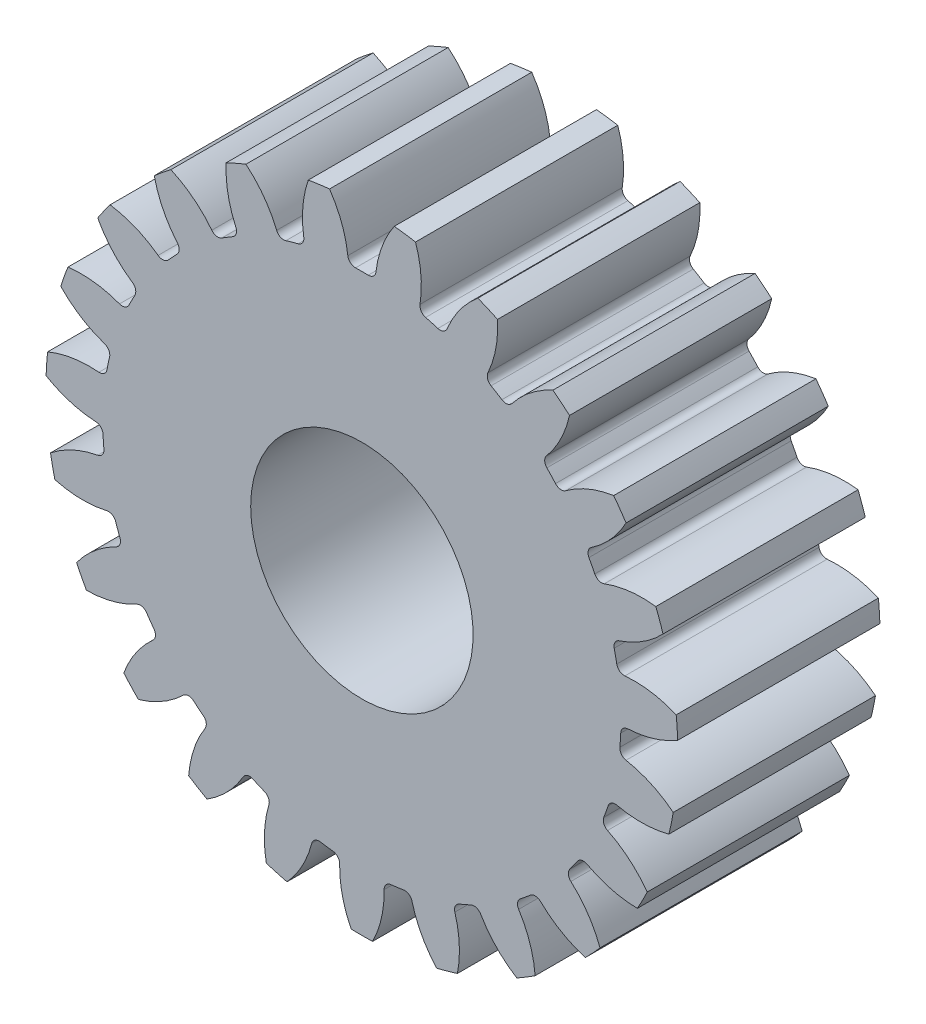
SolidWorks part; units mm, degrees
ref_plane "Front Plane" through (0, 0, 0) normal (0, 0, 1) x (1, 0, 0)
ref_plane "Top Plane" through (0, 0, 0) normal (0, 1, 0) x (1, 0, 0)
ref_plane "Right Plane" through (0, 0, 0) normal (1, 0, 0) x (0, 0, -1)
sketch "Sketch2" plane through (0, 0, 0) normal (0, 0, 1) x (1, 0, 0)
  circle A0 centre (0, 0) radius 14.375 construction
  circle A1 centre (0, 0) radius 15.625
  dimension "D1" = 28.75
  dimension "D2" = 31.25
extrude "Boss-Extrude1" add sketch "Sketch2" along normal mid plane 10 contours A1
sketch "Sketch3" plane through (0, 0, 0) normal (0, 0, 1) x (1, 0, 0)
  line L0 (0, 15.625) -> (0, 0) construction
  line L1 (0, 0) -> (4.2156, 15.0456) construction
  line L2 (0, 0) -> (2.1276, 15.4795) construction
  line L3 (-0.6666, 12.7951) -> (0, 0) construction
  line L4 (-0.981, 14.3415) -> (0.981, 14.3415) construction
  line L5 (0.981, 14.3415) -> (2.9247, 14.0743) construction
  line L6 (-1.4245, 15.5599) -> (0, 11.6463) construction
  circle A0 centre (0, 0) radius 13.125 construction
  arc A1 (0.6666, 12.7951) -> (-0.6666, 12.7951) centre (0, 0) ccw
  circle A2 centre (0, 0) radius 15.625 construction
  circle A3 centre (0, 0) radius 14.375 construction
  arc A4 (-1.6005, 15.5428) -> (-0.6666, 12.7951) centre (-5.9918, 12.5177) cw
  arc A5 (1.6005, 15.5428) -> (0.6666, 12.7951) centre (5.9918, 12.5177) ccw
  arc A6 (1.6005, 15.5428) -> (-1.6005, 15.5428) centre (0, 0) ccw
  dimension "D4" = 28.75
  dimension "D1" = 15.652
  dimension "D2" = 2.5
  dimension "D3" = 2.8125
  dimension "D5" = 20
extrude "Cut-Extrude1" cut sketch "Sketch3" against normal through all both and the other way through all
fillet "Fillet1" radius 0.375 2 edges at (0.6666, 12.7951, 0) (-0.6666, 12.7951, 0)
ref_axis "Axis1" through (0, 0, -11) along (0, 0, 1)
pattern_circular "CirPattern1" count 23 over 360 about axis through (0, 0, -11) along (0, 0, 1) of "Cut-Extrude1", "Fillet1"
sketch "Sketch4" plane through (0, 0, -5) normal (0, 0, -1) x (-1, 0, 0)
  circle A0 centre (0, 0) radius 5.5
  dimension "D1" = 11
extrude "Cut-Extrude3" cut sketch "Sketch4" against normal blind 10
equation "\"Module\"= 1.25mm"
equation "\"Number of teeth\"= 23"
equation "\"pressure angle\"= 20"
equation "\"D1@Sketch2\"=\"Module\"*\"Number of teeth\""
equation "\"D2@Sketch2\"=(\"Number of teeth\"+2) *\"Module\""
equation "\"D1@Sketch3\"=360 /\"Number of teeth\""
equation "\"D2@Sketch3\"=\"Module\"*2"
equation "\"D3@Sketch3\"=\"Module\" *if( \"Module\"=> 1.25,2.25,2.4)"
equation "\"D5@Sketch3\"=\"pressure angle\""
equation "\"D4@Sketch3\"=\"Module\"*\"Number of teeth\""
equation "\"D1@CirPattern1\"=\"Number of teeth\""
equation "\"D1@Fillet1\"=0.3 *\"Module\""
